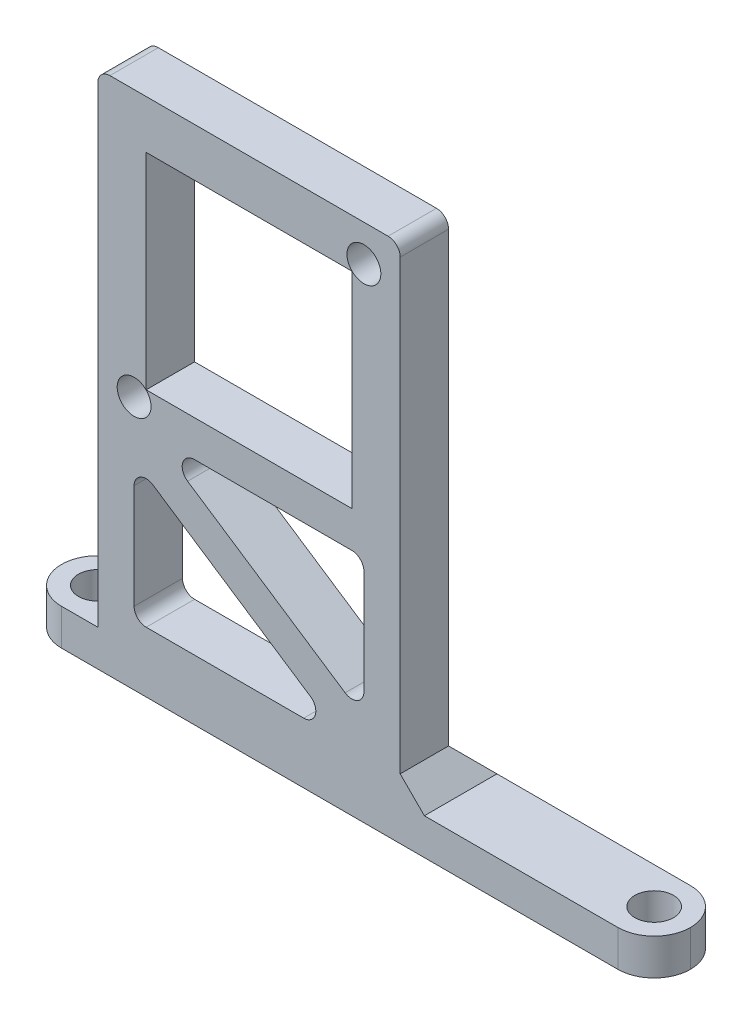
SolidWorks part; units mm, degrees
ref_plane "Front Plane" through (0, 0, 0) normal (0, 0, 1) x (1, 0, 0)
ref_plane "Top Plane" through (0, 0, 0) normal (0, 1, 0) x (1, 0, 0)
ref_plane "Right Plane" through (0, 0, 0) normal (1, 0, 0) x (0, 0, -1)
sketch "Sketch1" plane through (0, 0, 0) normal (0, 1, 0) x (1, 0, 0)
  line L1 (26, 3) -> (-26, 3)
  line L2 (26, 3) -> (26, -3)
  line L3 (26, -3) -> (-26, -3)
  line L4 (-26, 3) -> (-26, -3)
  line L5 (26, 3) -> (-26, -3) construction
  line L6 (26, -3) -> (-26, 3) construction
  point P0 (0, 0)
  dimension "D1" = 52
  dimension "D2" = 6
extrude "Boss-Extrude1" add sketch "Sketch1" along normal blind 3
sketch "Sketch2" plane through (0, 3, 0) normal (0, 1, 0) x (1, 0, 0)
  line L1 (-20, 1) -> (5, 1)
  line L2 (-20, 1) -> (-20, -3)
  line L3 (-20, -3) -> (5, -3)
  line L4 (5, 1) -> (5, -3)
  line L5 (-26, -3) -> (26, -3) construction
  line L6 (-26, 3) -> (-26, -3) construction
  dimension "D1" = 25
  dimension "D2" = 4
  dimension "D3" = 6
extrude "Boss-Extrude2" add sketch "Sketch2" along normal blind 40
sketch "Sketch3" plane through (0, 3, 0) normal (0, 1, 0) x (1, 0, 0)
  line L0 (0, 0) -> (50000, 0) construction
  line L1 (0, 0) -> (0, 50000) construction
  circle A0 centre (-23, 0) radius 1.6
  circle A1 centre (23, 0) radius 1.6
  dimension "D1" = 3.2
  dimension "D2" = 46
extrude "Cut-Extrude1" cut sketch "Sketch3" against normal through all
fillet "Fillet1" radius 3 4 edges at (26, 1.5, -3) (26, 1.5, 3) (-26, 1.5, 3) (-26, 1.5, -3)
sketch "Sketch5" plane through (0, 0, 3) normal (0, 0, 1) x (1, 0, 0)
  circle A0 centre (2, 40) radius 1.4
  circle A1 centre (-17, 21) radius 1.4
  dimension "D1" = 2.8
extrude "Cut-Extrude3" cut sketch "Sketch5" against normal through all
sketch "Sketch6" plane through (0, 0, 3) normal (0, 0, 1) x (1, 0, 0)
  line L0 (0.5, 38.5) -> (-15.5, 38.5) construction
  line L1 (-16, 39) -> (1, 39)
  line L2 (-16, 39) -> (-16, 22)
  line L3 (-16, 22) -> (1, 22)
  line L4 (1, 39) -> (1, 22)
  line L5 (-15.5, 22.5) -> (0.5, 22.5) construction
  line L6 (0.5, 22.5) -> (0.5, 38.5) construction
  line L7 (-15.5, 38.5) -> (-15.5, 22.5) construction
  dimension "D1" = 0.5
  dimension "D2" = 0.5
  dimension "D3" = 0.5
  dimension "D4" = 0.5
extrude "Cut-Extrude4" cut sketch "Sketch6" against normal through all
chamfer "Chamfer1" distance 2 angle 45 2 edges at (-7.5, 3, -1)
sketch "Sketch7" plane through (0, 0, -1) normal (0, 0, -1) x (-1, 0, 0)
  line L0 (-2, 19) -> (-2, 7.5002)
  line L1 (-2, 7.5002) -> (15.3421, 19)
  line L2 (15.3421, 19) -> (-2, 19)
  line L3 (17, 16.4998) -> (-0.3421, 5)
  line L4 (-0.3421, 5) -> (17, 5)
  line L5 (17, 5) -> (17, 16.4998)
  line L7 (-5, 43) -> (-5, 5) construction
  line L8 (20, 43) -> (20, 5) construction
  line L9 (16, 22) -> (-1, 22) construction
  line L10 (14.9004, 19.6661) -> (24037.5092, -36207.3068) construction
  line L11 (6.811, -5.7871) -> (24029.4199, -36232.7599) construction
  line L12 (-5, 5) -> (20, 5) construction
  dimension "D1" = 3
  dimension "D2" = 3
  dimension "D3" = 3
  dimension "D4" = 3
extrude "Cut-Extrude5" cut sketch "Sketch7" against normal through all
fillet "Fillet2" radius 1 8 edges at (-17, 5, 1) (-17, 16.4998, 1) (0.3421, 5, 1) (2, 7.5002, 1) (2, 19, 1) (-15.3421, 19, 1) (5, 43, 1) (-20, 43, 1)
